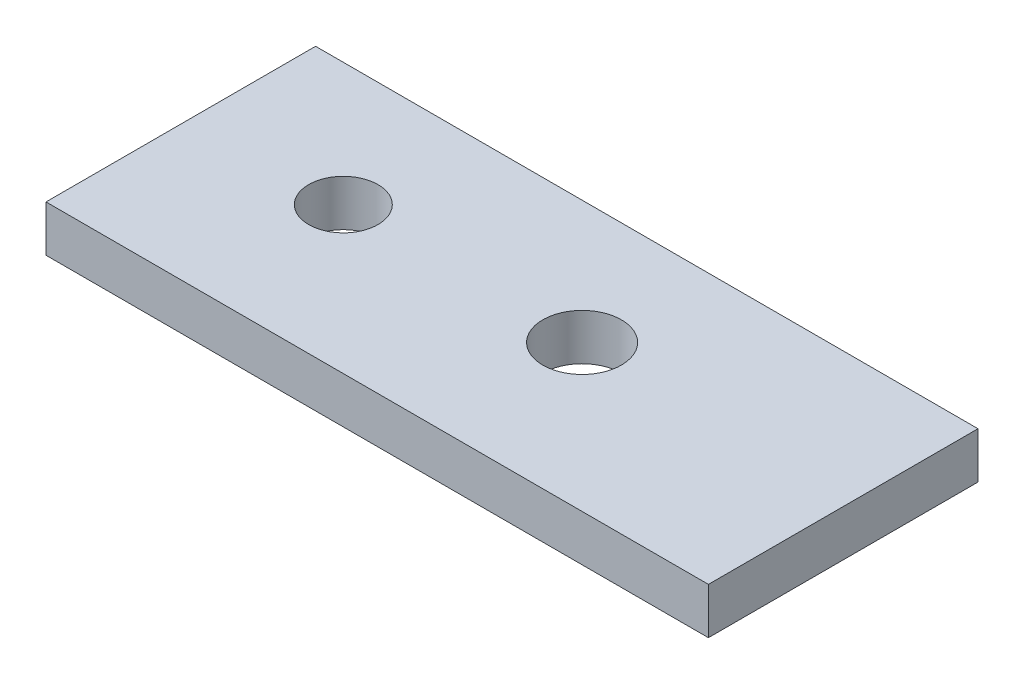
SolidWorks part; units mm, degrees
material "Maple"
ref_plane "Front Plane" through (0, 0, 0) normal (0, 0, 1) x (1, 0, 0)
ref_plane "Top Plane" through (0, 0, 0) normal (0, 1, 0) x (1, 0, 0)
ref_plane "Right Plane" through (0, 0, 0) normal (1, 0, 0) x (0, 0, -1)
sketch "Sketch1" plane through (0, 0, 0) normal (0, 1, 0) x (1, 0, 0)
  line L1 (0, 0) -> (86, 0)
  line L2 (0, 0) -> (0, 35)
  line L3 (0, 35) -> (86, 35)
  line L4 (86, 0) -> (86, 35)
  dimension "D2" = 35
extrude "Boss-Extrude1" add sketch "Sketch1" along normal blind 6
ref_plane "Plane1" through (0, 3, 0) normal (0, 1, 0) x (1, 0, 0)
sketch "Sketch2" plane through (0, 6, 0) normal (0, 1, 0) x (1, 0, 0)
  circle A0 centre (50.6, 19) radius 5.1
  circle A1 centre (19.6, 19) radius 4.5
  circle A4 centre (50.6, 19) radius 4 construction
  circle A5 centre (19.6, 19) radius 4 construction
  dimension "D1" = 9
  dimension "D2" = 10.2
extrude "Cut-Extrude1" cut sketch "Sketch2" against normal blind 6
